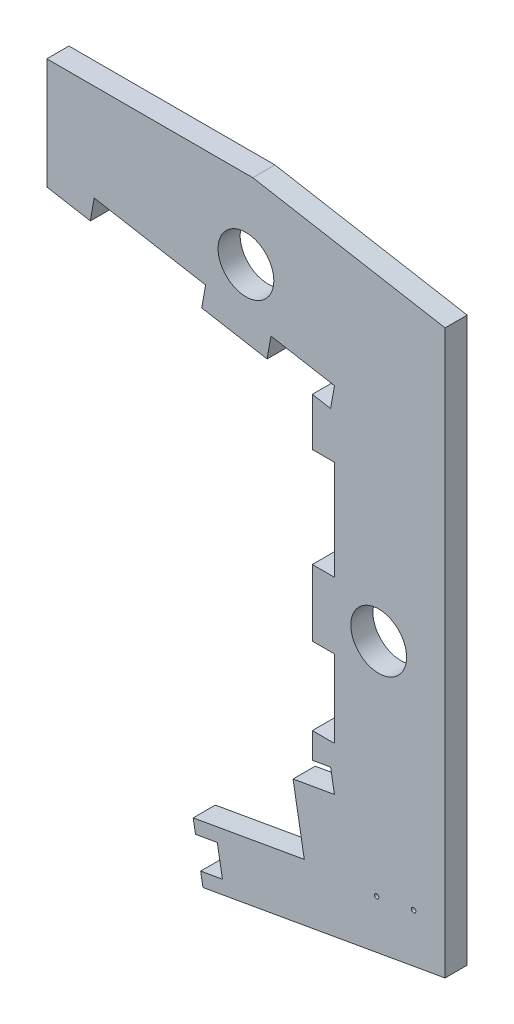
SolidWorks part; units mm, degrees
material "Balsa"
ref_plane "Plan de face" through (0, 0, 0) normal (0, 0, 1) x (1, 0, 0)
ref_plane "Plan de dessus" through (0, 0, 0) normal (0, 1, 0) x (1, 0, 0)
ref_plane "Plan de droite" through (0, 0, 0) normal (1, 0, 0) x (0, 0, -1)
sketch "Esquisse1" plane through (0, 0, 0) normal (0, 0, 1) x (1, 0, 0)
  line L0 (-65, 51.4613) -> (0, 40)
  line L1 (0, 40) -> (0, -40)
  line L2 (-6.8091, -56.1122) -> (-9.3591, -41.6503)
  line L3 (-9.3591, -41.6503) -> (0, -40)
  line L4 (-6.8091, -56.1122) -> (-31.9182, -60.5396)
  line L5 (-29.71, -73.063) -> (25, -63.4162)
  line L6 (25, -63.4162) -> (25, 63.8008)
  line L7 (25, 63.8008) -> (-18.4444, 71.4613)
  line L8 (-65, 71.4613) -> (-65, 51.4613)
  line L9 (7.1417, -5.2313) -> (92.0944, -5.2313) construction
  line L10 (-31.9182, -60.5396) -> (-29.71, -73.063)
  line L11 (-18.4444, 71.4613) -> (-65, 71.4613)
  line L12 (-18.4444, 71.4613) -> (-20, 53.6808) construction
  circle A0 centre (-20, 53.6808) radius 6.3
  circle A1 centre (10, -5) radius 6.3
  point P4 (-29.6197, 71.4613)
  point P19 (-7.4389, 69.5207)
  dimension "D1" = 12.6
  dimension "D15" = 12.6
  dimension "D2" = 10
  dimension "D3" = 20
  dimension "D4" = 80
  dimension "D5" = 65
  dimension "D6" = 100
  dimension "D7" = 100
  dimension "D8" = 85
  dimension "D9" = 35
  dimension "D10" = 90
  dimension "D11" = 9.5035
  dimension "D12" = 14.685
  dimension "D13" = 10
  dimension "D14" = 35
  dimension "D16" = 12.7166
  dimension "D17" = 100
  dimension "D18" = 100
  dimension "D19" = 20
extrude "Boss.-Extru.1" add sketch "Esquisse1" along normal blind 5
sketch "Esquisse2" plane through (0, 0, 0) normal (0, 0, -1) x (-1, 0, 0)
  line L0 (31.3966, -63.498) -> (30.231, -70.1086)
  line L1 (31.3966, -63.498) -> (26.4726, -62.6297)
  line L2 (30.231, -70.1086) -> (25.3069, -69.2404)
  line L3 (26.4726, -62.6297) -> (25.3069, -69.2404)
  line L5 (-16.8787, -72.4038) -> (-12.3995, -47.0007) construction
  line L11 (31.9182, -60.5396) -> (29.71, -73.063) construction
  line L12 (6.8091, -56.1122) -> (31.9182, -60.5396) construction
  circle A0 centre (-9.5242, -55.1691) radius 0.5
  circle A1 centre (-17.8951, -53.6931) radius 0.5
  dimension "D2" = 5
  dimension "D3" = 3.004
  dimension "D4" = 3
extrude "Enlèv. mat.-Extru.1" cut sketch "Esquisse2" against normal blind 5
sketch "Esquisse3" plane through (0, 0, 0) normal (0, 0, 1) x (1, 0, 0)
  line L0 (0, -40) -> (0, -30)
  line L1 (0, 40) -> (0, -40) construction
  line L2 (0, -40) -> (-9.3591, -41.6503) construction
  line L3 (0, -30) -> (-5, -30)
  line L4 (-5, -30) -> (-5, -35.8045)
  line L5 (-5, -35.8045) -> (-0.8682, -35.076)
  line L6 (-0.8682, -35.076) -> (0, -40)
  line L7 (0, 0) -> (-23.4139, 0) construction
  line L8 (0, 2.5) -> (-5, 2.5)
  line L9 (0, 2.5) -> (0, -12.5)
  line L10 (0, -12.5) -> (-5, -12.5)
  line L11 (-5, 2.5) -> (-5, -12.5)
  line L12 (0, 40) -> (0, -40) construction
  line L13 (-0.8682, 35.076) -> (0, 40)
  line L14 (-5, 35.8045) -> (-0.8682, 35.076)
  line L15 (-5, 25) -> (-5, 35.8045)
  line L16 (0, 25) -> (-5, 25)
  line L17 (0, 40) -> (0, 25)
  line L18 (-29.1225, 45.1351) -> (-14.3504, 42.5304)
  line L19 (-65, 51.4613) -> (0, 40) construction
  line L20 (-14.3504, 42.5304) -> (-15.2187, 37.6063)
  line L21 (-15.2187, 37.6063) -> (-29.9908, 40.2111)
  line L22 (-29.9908, 40.2111) -> (-29.1225, 45.1351)
  line L23 (-65, 51.4613) -> (-65, 46.3841)
  line L24 (-65, 46.3841) -> (-55.1519, 44.6476)
  line L25 (-55.1519, 44.6476) -> (-54.2837, 49.5717)
  line L26 (-54.2837, 49.5717) -> (-65, 51.4613)
  line L27 (-65, 71.4613) -> (-65, 51.4613) construction
  circle A0 centre (10, -5) radius 6.3 construction
  circle A1 centre (-20, 53.6808) radius 6.3 construction
  dimension "D1" = 10
  dimension "D2" = 5
  dimension "D3" = 5
  dimension "D4" = 10
  dimension "D5" = 5
  dimension "D6" = 7.5
  dimension "D7" = 15
  dimension "D8" = 15
  dimension "D9" = 5
  dimension "D10" = 15
  dimension "D11" = 7.5
  dimension "D12" = 5
  dimension "D13" = 10
extrude "Boss.-Extru.3" add sketch "Esquisse3" along normal blind 5
